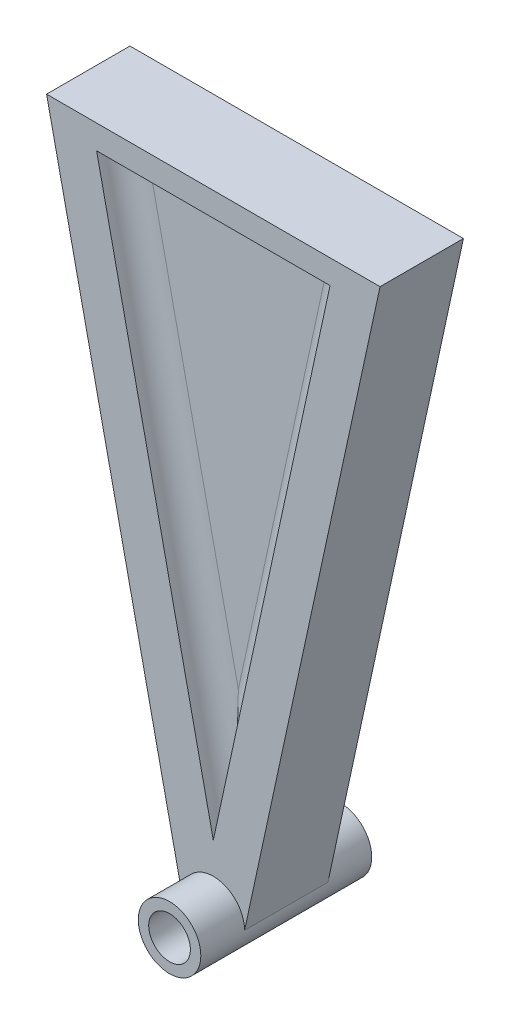
SolidWorks part; units mm, degrees
material "Cast Alloy Steel"
ref_plane "Front Plane" through (0, 0, 0) normal (0, 0, 1) x (1, 0, 0)
ref_plane "Top Plane" through (0, 0, 0) normal (0, 1, 0) x (1, 0, 0)
ref_plane "Right Plane" through (0, 0, 0) normal (1, 0, 0) x (0, 0, -1)
sketch "Sketch1" plane through (0, 0, 0) normal (0, 0, 1) x (1, 0, 0)
  circle A0 centre (0, 0) radius 5
  circle A1 centre (0, 0) radius 7.5
  dimension "D1" = 10
  dimension "D2" = 15
extrude "Boss-Extrude1" add sketch "Sketch1" along normal blind 41
sketch "Sketch2" plane through (0, 0, 0) normal (0, 1, 0) x (1, 0, 0)
  line L0 (5, 0) -> (-5, 0) construction
  line L1 (-40, -10.5) -> (40, -10.5)
  line L2 (-40, -10.5) -> (-40, -30.5)
  line L3 (-40, -30.5) -> (40, -30.5)
  line L4 (40, -10.5) -> (40, -30.5)
  dimension "D1" = 20
  dimension "D2" = 80
  dimension "D3" = 40
  dimension "D4" = 10.5
extrude "Boss-Extrude2" add sketch "Sketch2" along normal blind 150
sketch "Sketch3" plane through (0, 0, 0) normal (0, 0, -1) x (-1, 0, 0)
  circle A0 centre (0, 0) radius 5
extrude "Cut-Extrude1" cut sketch "Sketch3" against normal blind 150
sketch "Sketch4" plane through (0, 0, 10.5) normal (0, 0, -1) x (-1, 0, 0)
  line L0 (7.5, 0) -> (40, 150)
  line L1 (40, 150) -> (40, 0) construction
  line L2 (-40, 150) -> (40, 150) construction
  line L3 (40, 150) -> (40, 0)
  line L4 (40, 0) -> (7.5, 0)
extrude "Cut-Extrude2" cut sketch "Sketch4" against normal blind 150
mirror "Mirror1" about plane through (0, 0, 0) normal (1, 0, 0) of "Cut-Extrude2"
sketch "Sketch5" plane through (0, 0, 30.5) normal (0, 0, 1) x (1, 0, 0)
  line L0 (-28, 144.2308) -> (0, 15)
  line L1 (-40, 150) -> (-7.5, 0) construction
  line L2 (-28, 144.2308) -> (28, 144.2308)
  line L3 (0, 0) -> (0, 187.7227) construction
  line L4 (0, 15) -> (28, 144.2308)
  line L5 (40, 150) -> (7.5, 0) construction
  dimension "D1" = 12
  dimension "D2" = 12
  dimension "D3" = 15
extrude "Cut-Extrude3" cut sketch "Sketch5" against normal blind 6
ref_plane "Plane1" through (0, 0, 20) normal (0, 0, 1) x (1, 0, 0)
mirror "Mirror2" about plane through (0, 0, 20) normal (0, 0, 1) of "Cut-Extrude3"
fillet "Fillet1" radius 6 6 edges at (14, 79.6154, 24.5) (-14, 79.6154, 24.5) (0, 144.2308, 24.5) (14, 79.6154, 15.5) (-14, 79.6154, 15.5) (0, 144.2308, 15.5)
